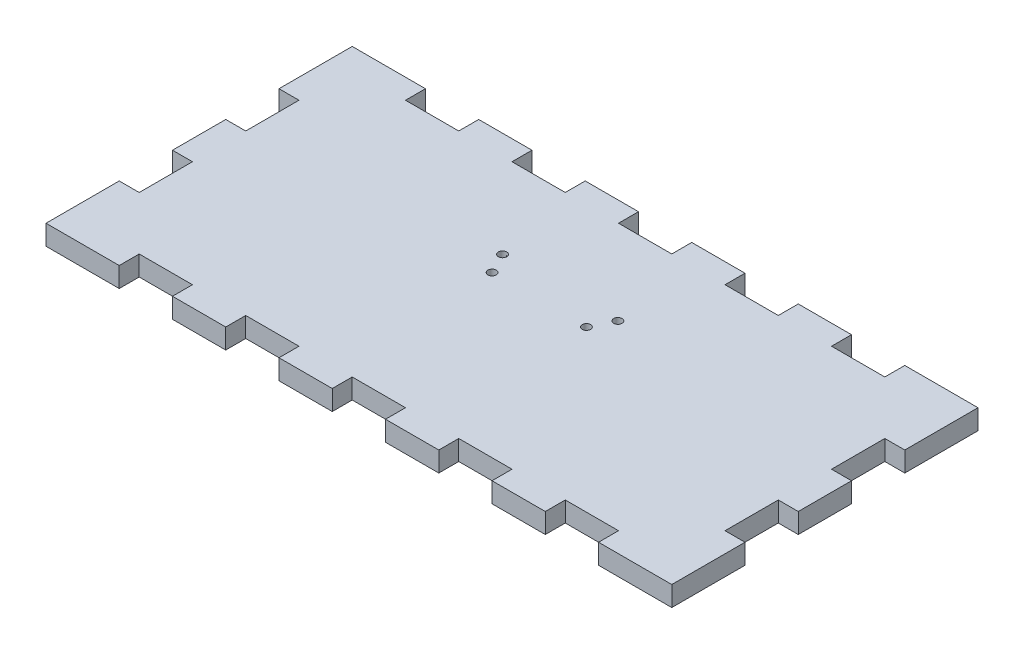
SolidWorks part; units mm, degrees
ref_plane "Front Plane" through (0, 0, 0) normal (0, 0, 1) x (1, 0, 0)
ref_plane "Top Plane" through (0, 0, 0) normal (0, 1, 0) x (1, 0, 0)
ref_plane "Right Plane" through (0, 0, 0) normal (1, 0, 0) x (0, 0, -1)
sketch "Sketch2" plane through (0, 0, 0) normal (0, 1, 0) x (1, 0, 0)
  line L1 (139.7, -63.5) -> (-139.7, -63.5)
  line L2 (139.7, -63.5) -> (139.7, 63.5)
  line L3 (139.7, 63.5) -> (-139.7, 63.5)
  line L4 (-139.7, -63.5) -> (-139.7, 63.5)
  line L5 (139.7, -63.5) -> (-139.7, 63.5) construction
  line L6 (139.7, 63.5) -> (-139.7, -63.5) construction
  point P0 (0, 0)
  dimension "D1" = 279.4
  dimension "D2" = 127
extrude "Boss-Extrude1" add sketch "Sketch2" along normal blind 9.525
sketch "Sketch3" plane through (0, 0, 63.5) normal (0, 0, 1) x (1, 0, 0)
  line L0 (-139.7, 9.525) -> (139.7, 9.525) construction
  line L1 (-139.7, 0) -> (-114.3, 0)
  line L2 (-139.7, 0) -> (-139.7, 9.525)
  line L3 (-139.7, 9.525) -> (-114.3, 9.525)
  line L4 (-114.3, 0) -> (-114.3, 9.525)
  dimension "D1" = 25.4
extrude "Boss-Extrude2" add sketch "Sketch3" along normal blind 9.525
pattern_linear "LPattern1" count 6 spacing 50.8 along (1, 0, 0) of "Boss-Extrude2"
mirror "Mirror1" about plane through (0, 0, 0) normal (0, 0, 1) of "LPattern1"
sketch "Sketch4" plane through (139.7, 0, 0) normal (1, 0, 0) x (0, 0, -1)
  line L0 (-73.025, 0) -> (73.025, 0) construction
  line L1 (-63.5, 0) -> (-38.1, 0)
  line L2 (-63.5, 0) -> (-63.5, 9.525)
  line L3 (-63.5, 9.525) -> (-38.1, 9.525)
  line L4 (-38.1, 0) -> (-38.1, 9.525)
  line L5 (-73.025, 9.525) -> (73.025, 9.525) construction
  line L6 (-73.025, 0) -> (-73.025, 9.525) construction
  dimension "D1" = 9.525
  dimension "D2" = 25.4
extrude "Boss-Extrude3" add sketch "Sketch4" along normal blind 9.525
pattern_linear "LPattern2" count 3 spacing 50.8 along (0, 0, -1) of "Boss-Extrude3"
mirror "Mirror2" about plane through (0, 0, 0) normal (1, 0, 0) of "LPattern2"
sketch "Sketch6" plane through (0, 0, 63.5) normal (0, 0, 1) x (1, 0, 0)
  line L1 (149.225, 9.525) -> (139.7, 9.525)
  line L2 (149.225, 9.525) -> (149.225, 0)
  line L3 (149.225, 0) -> (139.7, 0)
  line L4 (139.7, 9.525) -> (139.7, 0)
extrude "Boss-Extrude4" add sketch "Sketch6" along normal blind 9.525
mirror "Mirror3" about plane through (0, 0, 0) normal (1, 0, 0) of "Boss-Extrude4"
mirror "Mirror4" about plane through (0, 0, 0) normal (0, 0, 1) of "Mirror3"
sketch "Sketch7" plane through (0, 9.525, 0) normal (0, 1, 0) x (1, 0, 0)
  circle A0 centre (-29.2864, 23.8119) radius 0.032
  circle A1 centre (-23.072, 14.7922) radius 0.1056
  circle A2 centre (27.5, 22.9863) radius 2
  circle A3 centre (22.5, 12.9863) radius 2
extrude "Cut-Extrude1" cut sketch "Sketch7" against normal through all
sketch "Sketch8" plane through (0, 9.525, 0) normal (0, 1, 0) x (1, 0, 0)
  circle A0 centre (-25.974, 23.4033) radius 0.0509
  circle A1 centre (-24.0521, 14.3728) radius 0.0812
  circle A2 centre (-27.5, 22.9863) radius 2
  circle A3 centre (-22.5, 12.9863) radius 2
extrude "Cut-Extrude3" cut sketch "Sketch8" against normal through all contours A2 A0 | A3 region at (-22.5, 9.525, -12.9863) region at (-27.501, 9.525, -22.986)
sketch "Sketch9" plane through (0, 0, 0) normal (0, -1, 0) x (1, 0, 0)
  circle A0 centre (-22.5, -12.9863) radius 3.81
  circle A1 centre (-27.5, -22.9863) radius 3.81
  circle A2 centre (22.5, -12.9863) radius 3.81
  circle A3 centre (27.5, -22.9863) radius 3.81
  dimension "D1" = 7.62
  dimension "D2" = 7.62
  dimension "D3" = 7.62
  dimension "D4" = 7.62
extrude "Cut-Extrude4" cut sketch "Sketch9" against normal blind 4.7625
